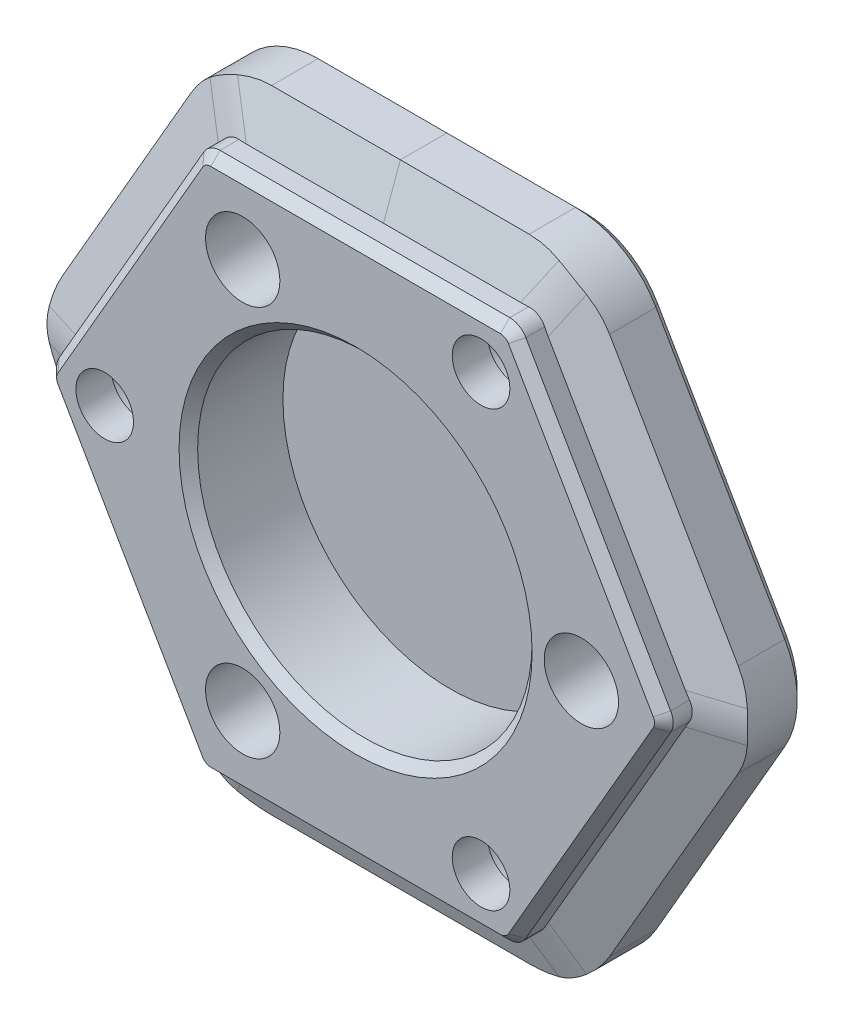
SolidWorks part; units mm, degrees
material "6061 合金"
ref_plane "前视基准面" through (0, 0, 0) normal (0, 0, 1) x (1, 0, 0)
ref_plane "上视基准面" through (0, 0, 0) normal (0, 1, 0) x (1, 0, 0)
ref_plane "右视基准面" through (0, 0, 0) normal (1, 0, 0) x (0, 0, -1)
other "Configuration Table"
sketch "草图2" plane through (0, 0, 0) normal (0, 0, 1) x (1, 0, 0)
  line L1 (8.3716, 14.5) -> (-8.3716, 14.5)
  line L2 (-8.3716, 14.5) -> (-16.7432, 0)
  line L3 (-16.7432, 0) -> (-8.3716, -14.5)
  line L4 (-8.3716, -14.5) -> (8.3716, -14.5)
  line L5 (8.3716, -14.5) -> (16.7432, 0)
  line L6 (16.7432, 0) -> (8.3716, 14.5)
  circle A0 centre (0, 0) radius 14.5 construction
  dimension "D1" = 29
extrude "凸台-拉伸1" add sketch "草图2" along normal blind 2.5 and the other way blind 5.5
hole_wizard "M3 六角圆柱头螺钉的柱形沉头孔1" positions "草图4" profile "草图5" counterbore size "M3" standard "GB" end condition through all
sketch "草图4" plane through (0, 0, -5.5) normal (0, 0, -1) x (-1, 0, 0)
  line L0 (-16.7432, 0) -> (0, 0) construction
  line L1 (0, 0) -> (-6.75, 11.6913) construction
  circle A0 centre (0, 0) radius 13.5
  point P0 (-6.75, 11.6913)
  point P24 (13.5, 0)
  point P25 (-6.75, -11.6913)
  dimension "D1" = 27
  dimension "D2" = 60
  dimension "D3" = 3
sketch "草图5" plane through (6.75, 11.6913, -5.5) normal (1, 0, 0) x (0, 1, 0)
  line L0 (0, 0) -> (0, 8)
  line L1 (0, 8) -> (1.55, 8)
  line L3 (1.55, 8) -> (1.55, 3.1)
  line L4 (1.55, 3.1) -> (2.35, 3.1)
  line L5 (2.35, 3.1) -> (2.35, 0)
  line L7 (2.35, 0) -> (0, 0)
  line L11 (0, -6.35) -> (0, 107.95) construction
  dimension "通孔孔直径" = 3.1
  dimension "通孔孔深度" = 8
  dimension "柱形沉头孔直径" = 4.7
  dimension "柱形沉头孔深度" = 3.1
hole_wizard "Ø4.0mm 暗销孔1" positions "草图6" profile "草图7" hole size "Ø4.0" standard "GB"
sketch "草图6" plane through (0, 0, 2.5) normal (0, 0, 1) x (1, 0, 0)
  line L0 (-23.5778, 0) -> (0, 0) construction
  line L1 (0, 0) -> (-6.075, 10.5222) construction
  circle A0 centre (0, 0) radius 12.15
  point P0 (-6.075, 10.5222)
  point P19 (12.15, 0)
  point P20 (-6.075, -10.5222)
  dimension "D1" = 24.3
  dimension "D2" = 60
  dimension "D3" = 3
sketch "草图7" plane through (-6.075, 10.5222, 2.5) normal (1, 0, 0) x (0, -1, 0)
  line L0 (0, 0) -> (0, 4.2017)
  line L1 (0, 4.2017) -> (2, 3)
  line L2 (2, 3) -> (2, 0)
  line L5 (2, 0) -> (0, 0)
  line L10 (0, 4.2017) -> (-2, 3) construction
  line L11 (0, -6.35) -> (0, 107.95) construction
  dimension "孔直径" = 4
  dimension "孔深度" = 3
  dimension "导头角度" = 118
sketch "草图8" plane through (0, 0, 2.5) normal (0, 0, 1) x (1, 0, 0)
  circle A0 centre (0, 0) radius 9
  dimension "D1" = 18
extrude "切除-拉伸1" cut sketch "草图8" against normal through all
ref_plane "基准面1" through (0, 0, -2.5) normal (0, 0, -1) x (-1, 0, 0)
sketch "草图10" plane through (0, 0, -2.5) normal (0, 0, -1) x (-1, 0, 0)
  line L6 (-8.3716, 14.5) -> (-16.7432, 0)
  line L7 (-16.7432, 0) -> (-8.3716, -14.5)
  line L9 (8.3716, -14.5) -> (16.7432, 0)
  line L11 (8.3716, 14.5) -> (-8.3716, 14.5)
  line L13 (-16.7432, 0) -> (-8.3716, -14.5)
  line L15 (8.3716, -14.5) -> (16.7432, 0)
  line L17 (8.3716, 14.5) -> (-8.3716, 14.5)
  line L22 (-8.3716, 14.5) -> (-16.7432, 0)
  line L25 (-8.3716, -14.5) -> (8.3716, -14.5)
  line L27 (-8.3716, -14.5) -> (8.3716, -14.5)
  line L28 (16.7432, 0) -> (8.3716, 14.5)
  line L29 (16.7432, 0) -> (8.3716, 14.5)
  dimension "D1" = 0
sketch "草图11" plane through (0, 0, 0) normal (1, 0, 0) x (0, 0, -1)
  line L0 (5.5, 0) -> (5.5, 14.5) construction
  line L1 (1.25, 16) -> (1.25, -0.3955) construction
  line L2 (-1, 14.5) -> (-0.0901, 17)
  line L3 (-2.5, 14.5) -> (5.5, 14.5) construction
  line L4 (-0.0901, 17) -> (2.5901, 17)
  line L5 (2.5901, 17) -> (3.5, 14.5)
  line L6 (3.5, 14.5) -> (-1, 14.5)
  dimension "D1" = 2.5
  dimension "D2" = 40
  dimension "D3" = 4.5
  dimension "D4" = 4.25
sweep "扫描1" add profiles "草图11" path "草图10"
fillet "圆角1" radius 5 18 edges at (9.815, 17, -1.25) (19.6299, 0, -1.25) (9.815, -17, -1.25) (-9.815, -17, -1.25) (-19.6299, 0, -1.25) (-9.815, 17, -1.25) (-9.0933, -15.75, -3.045) (9.0933, -15.75, -3.045) (18.1865, 0, -3.045) (9.0933, 15.75, -3.045) (-9.0933, 15.75, -3.045) (-18.1865, 0, -3.045) (9.0933, 15.75, 0.545) (-9.0933, 15.75, 0.545) (-18.1865, 0, 0.545) (-9.0933, -15.75, 0.545) (9.0933, -15.75, 0.545) (18.1865, 0, 0.545)
fillet "圆角2" radius 1 12 edges at (-8.3716, -14.5, 1.7108) (8.3716, -14.5, 1.7108) (16.7432, 0, 1.7108) (8.3716, 14.5, 1.7108) (-8.3716, 14.5, 1.7108) (-16.7432, 0, 1.7108) (-16.7432, 0, -4.4608) (-8.3716, -14.5, -4.4608) (8.3716, -14.5, -4.4608) (16.7432, 0, -4.4608) (8.3716, 14.5, -4.4608) (-8.3716, 14.5, -4.4608)
chamfer "倒角1" distance 0.5 angle 45 26 edges at (9, 0, 2.5) (9, 0, -5.5) (-12.5574, 7.25, 2.5) (-16.5885, 0, 2.5) (-8.2942, 14.366, 2.5) (-12.5574, -7.25, 2.5) (0, 14.5, 2.5) (-8.2942, -14.366, 2.5) (8.2942, 14.366, 2.5) (0, -14.5, 2.5) (12.5574, 7.25, 2.5) (8.2942, -14.366, 2.5) (16.5885, 0, 2.5) (12.5574, -7.25, 2.5) (0, 14.5, -5.5) (-8.2942, 14.366, -5.5) (8.2942, 14.366, -5.5) (-12.5574, 7.25, -5.5) (12.5574, 7.25, -5.5) (-16.5885, 0, -5.5) (16.5885, 0, -5.5) (12.5574, -7.25, -5.5) (-8.2942, -14.366, -5.5) (8.2942, -14.366, -5.5) (0, -14.5, -5.5) (-12.5574, -7.25, -5.5)
sketch "草图12" plane through (0, 0, -5.5) normal (0, 0, -1) x (-1, 0, 0)
  line L1 (-22.1926, 21.2914) -> (23.9387, 21.2914)
  line L2 (-22.1926, 21.2914) -> (-22.1926, -20.3338)
  line L3 (-22.1926, -20.3338) -> (23.9387, -20.3338)
  line L4 (23.9387, 21.2914) -> (23.9387, -20.3338)
extrude "切除-拉伸2" cut sketch "草图12" against normal up to vertex (2.9099 mm away) up to point (-6.9282, -17, -2.5901)
ref_plane "基准面2" through (-11.2583, 14.5, -2.5901) normal (0, 0, -1) x (-1, 0, 0)
sketch "草图15" plane through (-11.2583, 14.5, -2.5901) normal (0, 0, -1) x (-1, 0, 0)
  line L7 (0, -29) -> (6.9282, -17)
  line L8 (6.9282, -12) -> (0, 0)
  line L9 (-4.3301, 2.5) -> (-11.2583, 2.5)
  line L10 (-11.2583, 2.5) -> (-18.1865, 2.5)
  line L11 (-22.5167, 0) -> (-29.4449, -12)
  line L12 (-29.4449, -17) -> (-22.5167, -29)
  line L13 (-18.1865, -31.5) -> (-4.3301, -31.5)
  line L14 (0, -29) -> (6.9282, -17)
  line L15 (6.9282, -12) -> (0, 0)
  line L16 (-4.3301, 2.5) -> (-11.2583, 2.5)
  line L17 (-11.2583, 2.5) -> (-18.1865, 2.5)
  line L18 (-22.5167, 0) -> (-29.4449, -12)
  line L19 (-29.4449, -17) -> (-22.5167, -29)
  line L20 (-18.1865, -31.5) -> (-4.3301, -31.5)
  circle A0 centre (-18.0083, -26.1913) radius 2.35 construction
  circle A1 centre (2.2417, -14.5) radius 2.35 construction
  circle A2 centre (-18.0083, -2.8087) radius 2.35 construction
  circle A3 centre (-18.0083, -26.1913) radius 2.35
  circle A4 centre (2.2417, -14.5) radius 2.35
  circle A5 centre (-18.0083, -2.8087) radius 2.35
  arc A6 (6.9282, -17) -> (6.9282, -12) centre (2.5981, -14.5) ccw
  arc A7 (0, 0) -> (-4.3301, 2.5) centre (-4.3301, -2.5) ccw
  arc A8 (-18.1865, 2.5) -> (-22.5167, 0) centre (-18.1865, -2.5) ccw
  arc A9 (-29.4449, -12) -> (-29.4449, -17) centre (-25.1147, -14.5) ccw
  arc A10 (-22.5167, -29) -> (-18.1865, -31.5) centre (-18.1865, -26.5) ccw
  arc A11 (-4.3301, -31.5) -> (0, -29) centre (-4.3301, -26.5) ccw
  arc A12 (6.9282, -17) -> (6.9282, -12) centre (2.5981, -14.5) ccw
  arc A13 (0, 0) -> (-4.3301, 2.5) centre (-4.3301, -2.5) ccw
  arc A14 (-18.1865, 2.5) -> (-22.5167, 0) centre (-18.1865, -2.5) ccw
  arc A15 (-29.4449, -12) -> (-29.4449, -17) centre (-25.1147, -14.5) ccw
  arc A16 (-22.5167, -29) -> (-18.1865, -31.5) centre (-18.1865, -26.5) ccw
  arc A17 (-4.3301, -31.5) -> (0, -29) centre (-4.3301, -26.5) ccw
  dimension "D1" = 0
extrude "凸台-拉伸2" add sketch "草图15" along normal blind 0.32
sketch "草图16" plane through (0, 0, -2.4) normal (0, 0, -1) x (-1, 0, 0)
  circle A0 centre (-6.75, -11.6913) radius 2.35 construction
  circle A1 centre (13.5, 0) radius 2.35 construction
  circle A2 centre (-6.75, 11.6913) radius 2.35 construction
  circle A3 centre (-6.75, -11.6913) radius 2.35
  circle A4 centre (13.5, 0) radius 2.35
  circle A5 centre (-6.75, 11.6913) radius 2.35
extrude "切除-拉伸3" cut sketch "草图16" against normal blind 3
sketch "草图17" [suppressed] plane through (0, 0, -2.5901) normal (0, 0, 1) x (1, 0, 0)
  circle A1 centre (0, 0) radius 9
  circle A2 centre (0, 0) radius 9
  dimension "D1" = 0
extrude "切除-拉伸4" [suppressed] cut sketch "草图17" against normal blind 3
chamfer "倒角2" [suppressed] distance 0.5 angle 45
chamfer "倒角3" distance 0.5 angle 45 12 edges at (-14.7224, 8.5, -2.9101) (-9.4282, 16.3301, -2.9101) (-18.8564, 0, -2.9101) (0, 17, -2.9101) (-14.7224, -8.5, -2.9101) (9.4282, 16.3301, -2.9101) (-9.4282, -16.3301, -2.9101) (14.7224, 8.5, -2.9101) (0, -17, -2.9101) (18.8564, 0, -2.9101) (9.4282, -16.3301, -2.9101) (14.7224, -8.5, -2.9101)
